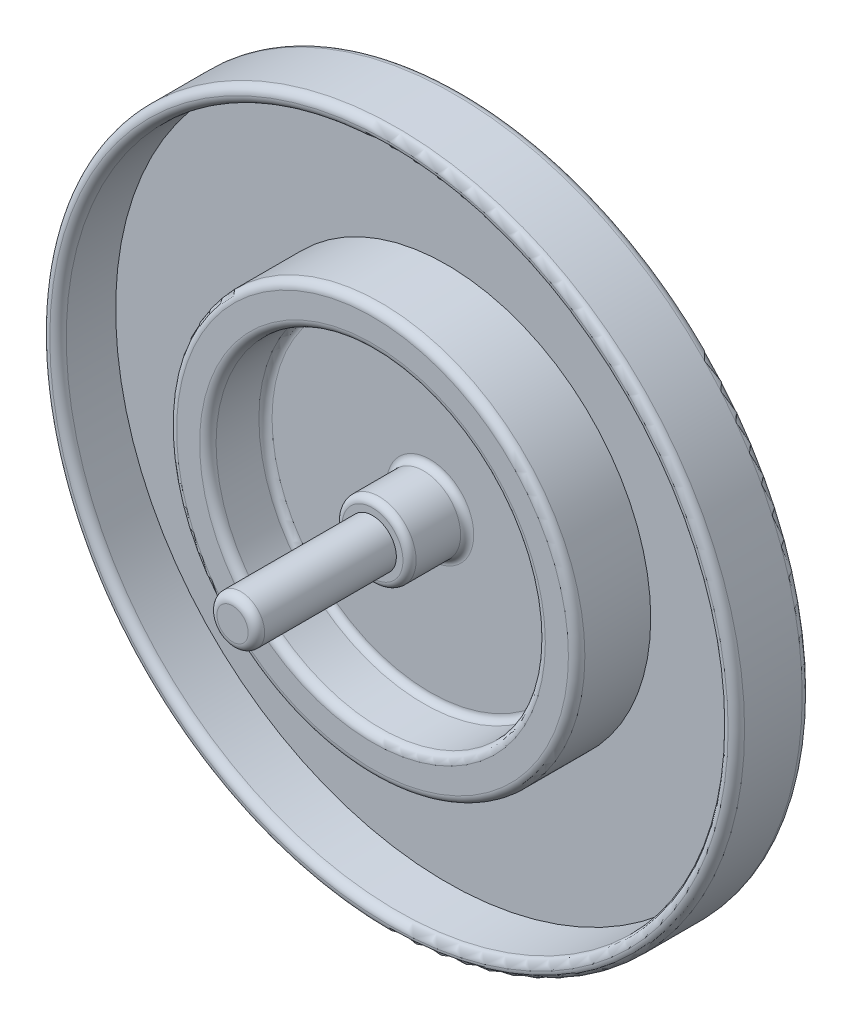
SolidWorks part; units mm, degrees
ref_plane "Front Plane" through (0, 0, 0) normal (0, 0, 1) x (1, 0, 0)
ref_plane "Top Plane" through (0, 0, 0) normal (0, 1, 0) x (1, 0, 0)
ref_plane "Right Plane" through (0, 0, 0) normal (1, 0, 0) x (0, 0, -1)
sketch "Sketch1" plane through (0, 0, 0) normal (0, 0, 1) x (1, 0, 0)
  circle A2 centre (0, 0) radius 12.4
  circle A3 centre (0, 0) radius 20.1
  circle A4 centre (0, 0) radius 10
  circle A5 centre (0, 0) radius 21.1
  dimension "D1" = 24.8
  dimension "D2" = 40.2
  dimension "D3" = 20
  dimension "D4" = 42.2
extrude "Boss-Extrude1" add sketch "Sketch1" along normal blind 4.5 contours A2 A4 | A5 A3 region at (-12.0493, 0, 0) region at (-20.5032, 0, 0)
sketch "Sketch6" plane through (0, 0, 4.5) normal (0, 0, 1) x (1, 0, 0)
  circle A0 centre (0, 0) radius 20.1 construction
  circle A1 centre (0, 0) radius 21.1
  circle A2 centre (0, 0) radius 21.1
  circle A3 centre (0, 0) radius 20.1
  dimension "D1" = 0
extrude "Cut-Extrude1" cut sketch "Sketch6" against normal blind 1
sketch "Sketch2" plane through (0, 0, 0) normal (0, 0, -1) x (-1, 0, 0)
  circle A0 centre (0, 0) radius 21.1 construction
  circle A1 centre (0, 0) radius 21.1
extrude "Boss-Extrude2" add sketch "Sketch2" along normal blind 1
sketch "Sketch3" plane through (0, 0, 0) normal (0, 0, 1) x (1, 0, 0)
  circle A0 centre (0, 0) radius 1.45
  dimension "D1" = 2.9
extrude "Boss-Extrude3" add sketch "Sketch3" along normal blind 13
fillet "Fillet1" radius 0.5 6 edges at (1.45, 0, 13) (10, 0, 4.5) (12.4, 0, 4.5) (-21.1, 0, -1) (20.1, 0, 3.5) (21.1, 0, 3.5)
sketch "Sketch4" plane through (0, 0, 0) normal (0, 0, 1) x (1, 0, 0)
  circle A0 centre (0, 0) radius 10 construction
  circle A1 centre (0, 0) radius 10
extrude "Boss-Extrude4" add sketch "Sketch4" along normal blind 1
sketch "Sketch5" plane through (0, 0, 1) normal (0, 0, 1) x (1, 0, 0)
  circle A0 centre (0, 0) radius 2.25
  circle A1 centre (0, 0) radius 1.45 construction
  dimension "D1" = 0.8
extrude "Boss-Extrude5" add sketch "Sketch5" along normal blind 3.5
fillet "Fillet2" radius 0.4 3 edges at (10, 0, 1) (2.25, 0, 4.5) (2.25, 0, 1)
